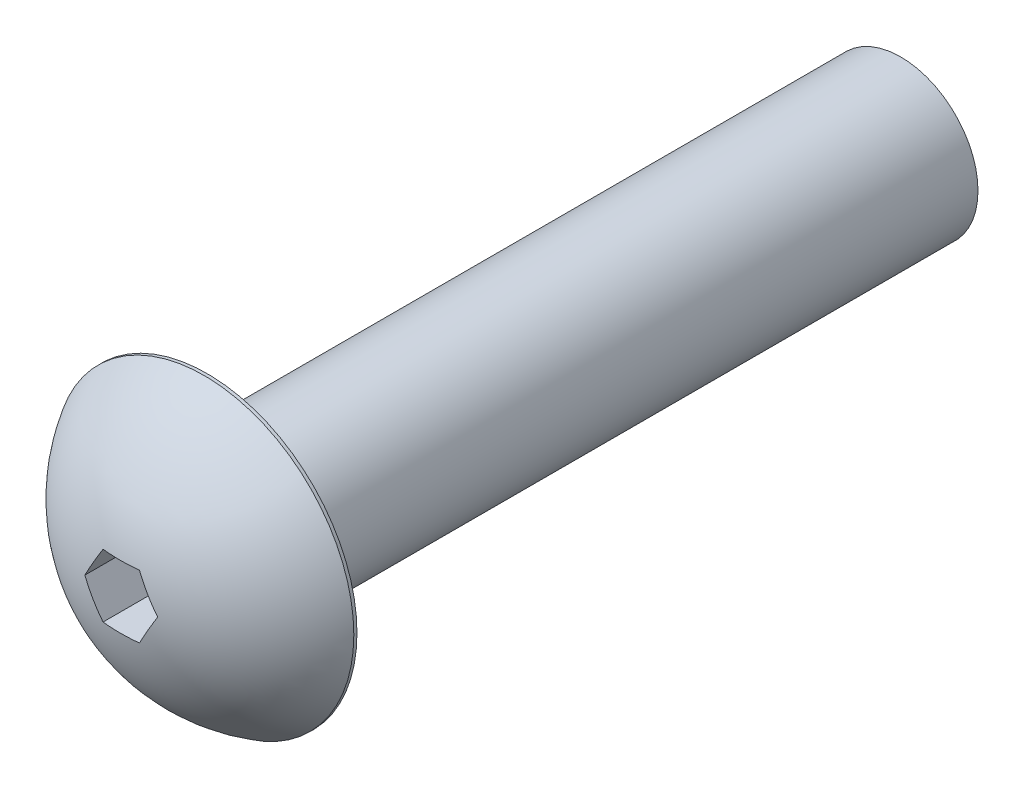
SolidWorks part; units mm, degrees
ref_plane "Front" through (0, 0, 0) normal (0, 0, 1) x (1, 0, 0)
ref_plane "Top" through (0, 0, 0) normal (0, 1, 0) x (1, 0, 0)
ref_plane "Right" through (0, 0, 0) normal (1, 0, 0) x (0, 0, -1)
sketch "Sketch1" plane through (0, 0, 0) normal (0, 0, 1) x (1, 0, 0)
  circle A0 centre (0, 0) radius 2.45
  dimension "D1" = 4.9
extrude "Boss-Shaft" add sketch "Sketch1" along normal blind 22
cosmetic thread "Cosmetic Thread1" parameters "D2"=1.993
sketch "Sketch2" plane through (0, 0, 22) normal (0, 0, 1) x (1, 0, 0)
  circle A0 centre (0, 0) radius 4.75
  dimension "D1" = 9.5
extrude "Boss-Head Base" add sketch "Sketch2" along normal blind 0.1
dome "Dome-M3" [suppressed] faces to dome 1 distance 2 parameters "D1"=2
dome "Dome-M5" faces to dome 1 distance 2.75 reverse direction no elliptical dome no face at (4.75, 0, 22.1) parameters "D1"=2.75
sketch "Sketch3" plane through (0, 0, 22) normal (0, 0, -1) x (-1, 0, 0)
  line L1 (-0.5774, 1) -> (-1.1547, 0)
  line L2 (-1.1547, 0) -> (-0.5774, -1)
  line L3 (-0.5774, -1) -> (0.5774, -1)
  line L4 (0.5774, -1) -> (1.1547, 0)
  line L5 (1.1547, 0) -> (0.5774, 1)
  line L6 (0.5774, 1) -> (-0.5774, 1)
  circle A0 centre (0, 0) radius 1 construction
  dimension "D1" = 2
extrude "Cut-Hex" cut sketch "Sketch3" against normal through all
